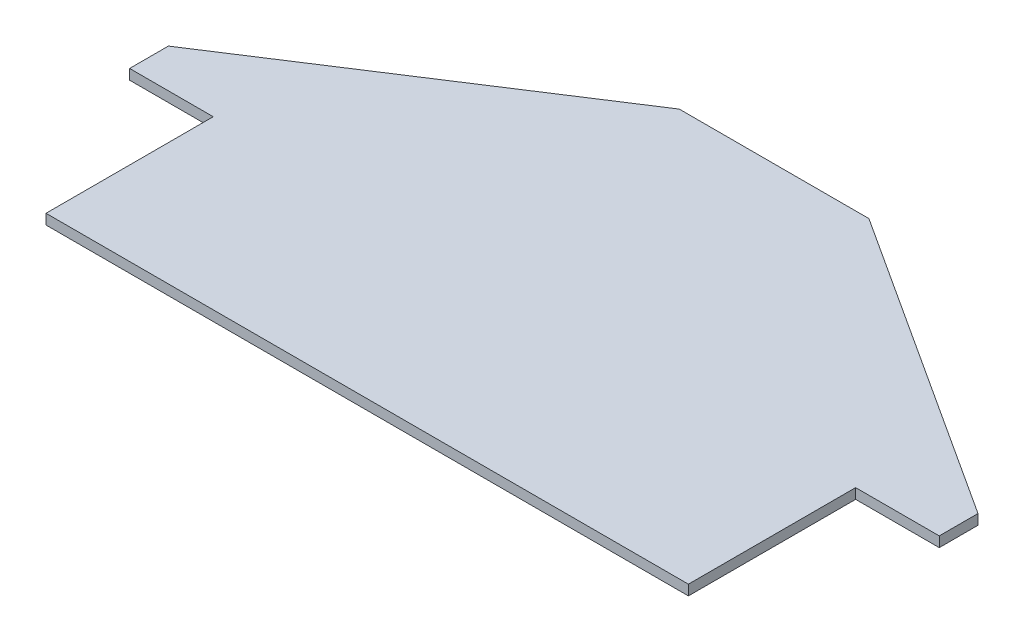
SolidWorks part; units mm, degrees
ref_plane "Front Plane" through (0, 0, 0) normal (0, 0, 1) x (1, 0, 0)
ref_plane "Top Plane" through (0, 0, 0) normal (0, 1, 0) x (1, 0, 0)
ref_plane "Right Plane" through (0, 0, 0) normal (1, 0, 0) x (0, 0, -1)
sketch "Sketch1" plane through (0, 0, 0) normal (0, 1, 0) x (1, 0, 0)
  line L0 (-80.01, 0) -> (80.01, 0)
  line L1 (80.01, 0) -> (80.01, 41.656)
  line L2 (80.01, 41.656) -> (100.838, 41.656)
  line L3 (100.838, 41.656) -> (100.838, 51.308)
  line L4 (100.838, 51.308) -> (23.622, 51.308) construction
  line L5 (23.622, 51.308) -> (23.622, 101.346) construction
  line L6 (100.838, 51.308) -> (23.622, 101.346)
  line L7 (0, 0) -> (0, 142.9083) construction
  line L8 (-23.622, 51.308) -> (-23.622, 101.346) construction
  line L9 (-100.838, 51.308) -> (-23.622, 51.308) construction
  line L10 (-100.838, 51.308) -> (-23.622, 101.346)
  line L11 (-100.838, 41.656) -> (-100.838, 51.308)
  line L12 (-80.01, 41.656) -> (-100.838, 41.656)
  line L13 (-80.01, 0) -> (-80.01, 41.656)
  line L14 (-23.622, 101.346) -> (23.622, 101.346)
  point P11 (0, 0)
  dimension "D1" = 80.01
  dimension "D2" = 41.656
  dimension "D3" = 20.828
  dimension "D4" = 9.652
  dimension "D5" = 77.216
  dimension "D6" = 50.038
extrude "Boss-Extrude1" add sketch "Sketch1" along normal blind 2.54
